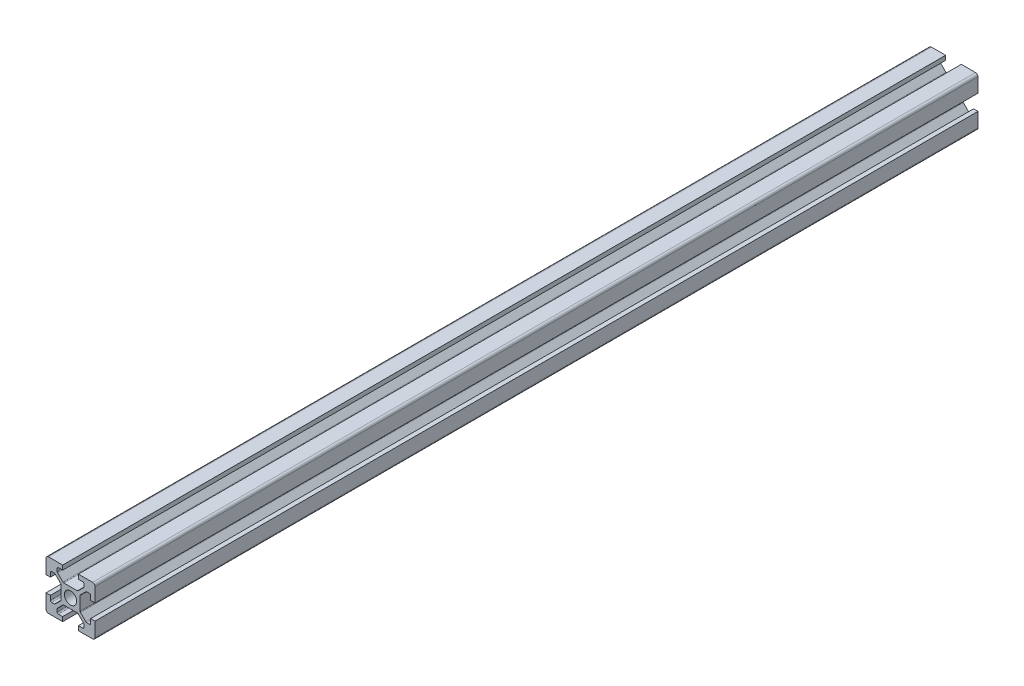
SolidWorks part; units mm, degrees
material "1060 Alloy"
ref_plane "Front Plane" through (0, 0, 0) normal (0, 0, 1) x (1, 0, 0)
ref_plane "Top Plane" through (0, 0, 0) normal (0, 1, 0) x (1, 0, 0)
ref_plane "Right Plane" through (0, 0, 0) normal (1, 0, 0) x (0, 0, -1)
sketch "Sketch1" plane through (0, 0, 0) normal (0, 0, 1) x (1, 0, 0)
  line L0 (20, 0) -> (-8.059, 28.059) construction
  line L1 (0, 0) -> (6.8, 0)
  line L2 (0, 0) -> (0, 6.8)
  line L3 (0, 20) -> (6.8, 20)
  line L4 (20, 0) -> (20, 6.8)
  line L5 (6.8, 20) -> (6.8, 18.2)
  line L6 (20, 20) -> (8.2322, 8.2322) construction
  line L7 (12.95, 6.1) -> (7.05, 6.1)
  line L8 (13.9, 7.05) -> (13.9, 12.95)
  line L9 (12.95, 13.9) -> (7.05, 13.9)
  line L10 (6.1, 7.05) -> (6.1, 12.95)
  line L11 (13.9, 6.1) -> (6.1, 13.9) construction
  line L12 (13.9, 13.9) -> (6.1, 6.1) construction
  line L13 (4.55, 16.4) -> (7.05, 13.9)
  line L14 (13.2, 18.2) -> (13.2, 20)
  line L15 (1.8, 6.8) -> (0, 6.8)
  line L16 (0, 13.2) -> (0, 20)
  line L17 (0, 13.2) -> (1.8, 13.2)
  line L18 (10, 10) -> (10, 13.9) construction
  line L19 (16.4, 4.55) -> (13.9, 7.05)
  line L20 (4.55, 16.4) -> (4.55, 18.2)
  line L21 (4.55, 18.2) -> (6.8, 18.2)
  line L22 (13.2, 18.2) -> (15.45, 18.2)
  line L23 (15.45, 18.2) -> (15.45, 16.4)
  line L24 (15.45, 16.4) -> (12.95, 13.9)
  line L25 (16.4, 4.55) -> (18.2, 4.55)
  line L26 (18.2, 4.55) -> (18.2, 6.8)
  line L27 (20, 6.8) -> (18.2, 6.8)
  line L28 (18.2, 13.2) -> (20, 13.2)
  line L29 (18.2, 13.2) -> (18.2, 15.45)
  line L30 (18.2, 15.45) -> (16.4, 15.45)
  line L31 (16.4, 15.45) -> (13.9, 12.95)
  line L32 (1.8, 4.55) -> (3.6, 4.55)
  line L33 (3.6, 15.45) -> (6.1, 12.95)
  line L34 (3.6, 15.45) -> (1.8, 15.45)
  line L35 (1.8, 15.45) -> (1.8, 13.2)
  line L36 (0, 13.2) -> (1.8, 13.2)
  line L37 (1.8, 6.8) -> (0, 6.8)
  line L38 (3.6, 4.55) -> (6.1, 7.05)
  line L39 (1.8, 6.8) -> (1.8, 4.55)
  line L40 (15.45, 3.6) -> (12.95, 6.1)
  line L41 (4.55, 3.6) -> (7.05, 6.1)
  line L42 (4.55, 1.8) -> (4.55, 3.6)
  line L43 (6.8, 1.8) -> (4.55, 1.8)
  line L44 (6.8, 1.8) -> (6.8, 0)
  line L45 (15.45, 3.6) -> (15.45, 1.8)
  line L46 (15.45, 1.8) -> (13.2, 1.8)
  line L47 (13.2, 0) -> (13.2, 1.8)
  line L48 (13.2, 20) -> (20, 20)
  line L49 (20, 13.2) -> (20, 20)
  line L50 (13.2, 0) -> (20, 0)
  line L51 (6.1, 6.1) -> (-5.5045, -5.5045) construction
  circle A0 centre (10, 10) radius 2.5
  point P25 (10, 16.4)
  point P39 (13.2, 19.1)
  point P46 (0.9, 6.8)
  dimension "D3" = 5
  dimension "D2" = 20
  dimension "D4" = 7.8
  dimension "D5" = 7.8
  dimension "D6" = 6.8
  dimension "D7" = 6.8
  dimension "D8" = 1.8
  dimension "D9" = 10.9
  dimension "D10" = 1.8
  dimension "D11" = 10.9
  dimension "D12" = 20
extrude "Boss-Extrude1" add sketch "Sketch1" along normal blind 360 contours L47 L50 L4 L27 L26 L25 L19 L8 L31 L30 L29 L28 L49 L48 L14 L22 L23 L24 L9 L13 L20 L21 L5 L3 L16 L17 L35 L34 L33 L10 L38 L32 L39 L15 L2 L1 L44 L43 L42 L41 L7 L40 L45 L46 A0 region at (0.2828, 3.4, 0)
fillet "Fillet1" radius 1 4 edges at (20, 20, 180) (20, 0, 180) (0, 0, 180) (0, 20, 180)
fillet "Fillet2" radius 0.5 6 edges at (4.55, 18.2, 180) (4.55, 16.4, 180) (7.05, 13.9, 180) (15.45, 18.2, 180) (15.45, 16.4, 180) (12.95, 13.9, 180)
fillet "Fillet3" radius 0.5 6 edges at (18.2, 15.45, 180) (16.4, 15.45, 180) (13.9, 12.95, 180) (18.2, 4.55, 180) (13.9, 7.05, 180) (16.4, 4.55, 180)
fillet "Fillet4" radius 0.5 6 edges at (1.8, 15.45, 180) (3.6, 15.45, 180) (6.1, 12.95, 180) (3.6, 4.55, 180) (1.8, 4.55, 180) (6.1, 7.05, 180)
fillet "Fillet5" radius 0.5 6 edges at (7.05, 6.1, 180) (4.55, 3.6, 180) (4.55, 1.8, 180) (15.45, 1.8, 180) (15.45, 3.6, 180) (12.95, 6.1, 180)
